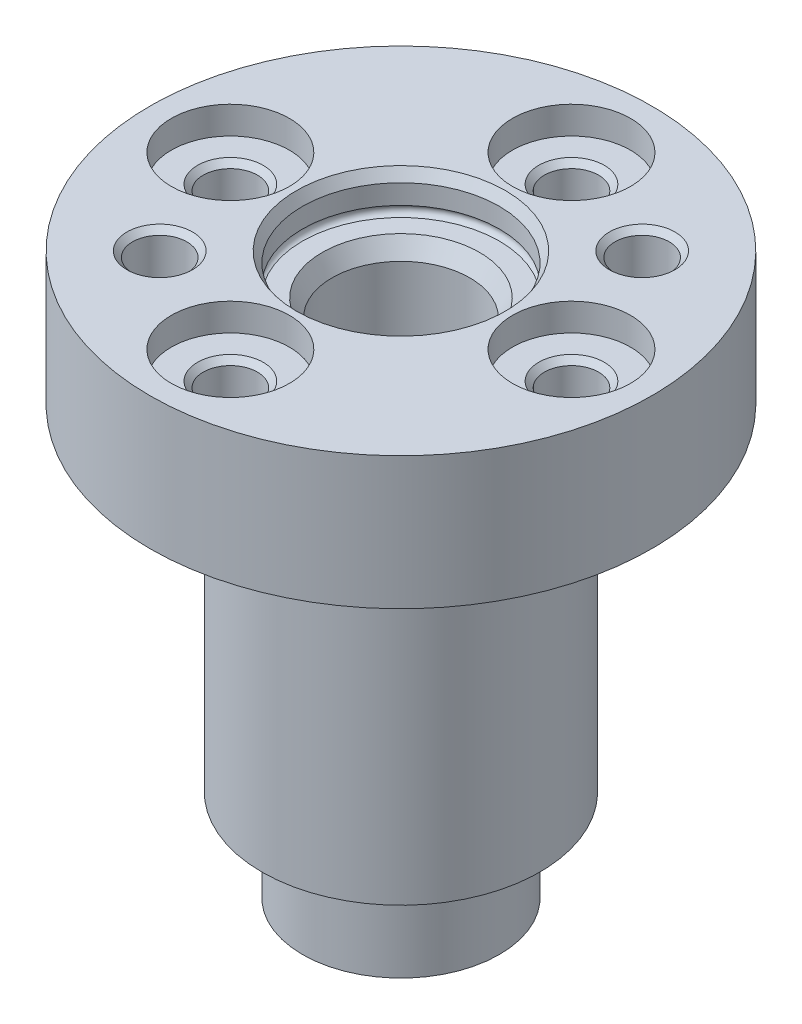
SolidWorks part; units mm, degrees
ref_plane "Front Plane" through (0, 0, 0) normal (0, 0, 1) x (1, 0, 0)
ref_plane "Top Plane" through (0, 0, 0) normal (0, 1, 0) x (1, 0, 0)
ref_plane "Right Plane" through (0, 0, 0) normal (1, 0, 0) x (0, 0, -1)
sketch "Sketch1" plane through (0, 0, 0) normal (0, 0, 1) x (1, 0, 0)
  line L0 (0, 42.7) -> (19.125, 42.7)
  line L1 (19.125, 42.7) -> (19.125, 32.6)
  line L2 (19.125, 32.6) -> (10.6, 32.6)
  line L3 (10.6, 32.6) -> (10.6, 7)
  line L4 (10.6, 7) -> (7.5, 7)
  line L5 (7.5, 7) -> (7.5, 0)
  line L6 (7.5, 0) -> (0, 0)
  line L7 (0, 0) -> (0, 42.7)
  line L8 (0, 0) -> (0, 42.7) construction
revolve "Revolve1" add sketch "Sketch1" angle 360 about L8 reverse direction yes
ref_plane "Plane1" through (0, 0, 0) normal (0, 0, -1) x (-1, 0, 0)
sketch "Sketch2" plane through (0, 0, 0) normal (0, 0, -1) x (-1, 0, 0)
  line L0 (0, 27.6) -> (17.125, 27.6)
  line L1 (17.125, 27.6) -> (17.125, 22.6)
  line L2 (17.125, 22.6) -> (0, 22.6)
  line L3 (0, 22.6) -> (0, 27.6)
  line L4 (0, 22.6) -> (0, 27.6) construction
revolve "Revolve2" add sketch "Sketch2" angle 4 about L4 other way angle 4 reverse direction yes
sketch "Sketch3" plane through (0, 0, 0) normal (0, 0, 1) x (1, 0, 0)
  line L0 (0, 42.7) -> (7.965, 42.7)
  line L1 (7.965, 42.7) -> (7.5, 41.8946)
  line L2 (7.5, 41.8946) -> (7.5, 40.4)
  line L3 (7.5, 39.6) -> (6.0006, 39.6)
  line L4 (6.0006, 39.6) -> (5.25, 38.3)
  line L5 (5.25, 38.3) -> (5.25, 1.5)
  line L6 (5.25, 1.5) -> (6.116, 0)
  line L7 (6.116, 0) -> (0, 0)
  line L8 (0, 0) -> (0, 42.7)
  line L9 (0, 0) -> (0, 42.7) construction
  arc A0 (7.5, 40.4) -> (7.5, 39.6) centre (7.3833, 40) cw
revolve "Cut-Revolve1" cut sketch "Sketch3" angle 360 about L9 reverse direction yes
sketch "Sketch4" plane through (0, 0, 0) normal (0, 0, 1) x (1, 0, 0)
  line L0 (13, 42.7) -> (17.5, 42.7)
  line L1 (17.5, 42.7) -> (17.5, 40.6)
  line L2 (17.5, 40.6) -> (15.5, 40.6)
  line L3 (15.5, 40.6) -> (15.067, 40.167)
  line L4 (15.067, 40.167) -> (15.067, 34.6)
  line L5 (15.067, 34.6) -> (13, 33.4066)
  line L6 (13, 33.4066) -> (13, 42.7)
  line L7 (13, 33.4066) -> (13, 42.7) construction
revolve "Cut-Revolve2" cut sketch "Sketch4" angle 360 about L7 reverse direction yes
cosmetic thread "Cosmetic Thread1" parameters "D1"=6, "D2"=5
sketch "Sketch5" plane through (0, 0, 0) normal (0, 0, 1) x (1, 0, 0)
  line L0 (-13, 42.7) -> (-8.5, 42.7)
  line L1 (-8.5, 42.7) -> (-8.5, 40.6)
  line L2 (-8.5, 40.6) -> (-10.5, 40.6)
  line L3 (-10.5, 40.6) -> (-10.933, 40.167)
  line L4 (-10.933, 40.167) -> (-10.933, 34.6)
  line L5 (-10.933, 34.6) -> (-13, 33.4066)
  line L6 (-13, 33.4066) -> (-13, 42.7)
  line L7 (-13, 33.4066) -> (-13, 42.7) construction
revolve "Cut-Revolve3" cut sketch "Sketch5" angle 360 about L7 reverse direction yes
cosmetic thread "Cosmetic Thread2" parameters "D1"=6, "D2"=5
sketch "Sketch6" plane through (0, 0, 0) normal (1, 0, 0) x (0, 0, -1)
  line L0 (13, 42.7) -> (17.5, 42.7)
  line L1 (17.5, 42.7) -> (17.5, 40.6)
  line L2 (17.5, 40.6) -> (15.5, 40.6)
  line L3 (15.5, 40.6) -> (15.067, 40.167)
  line L4 (15.067, 40.167) -> (15.067, 34.6)
  line L5 (15.067, 34.6) -> (13, 33.4066)
  line L6 (13, 33.4066) -> (13, 42.7)
  line L7 (13, 33.4066) -> (13, 42.7) construction
revolve "Cut-Revolve4" cut sketch "Sketch6" angle 360 about L7 reverse direction yes
cosmetic thread "Cosmetic Thread3" parameters "D1"=6, "D2"=5
sketch "Sketch7" plane through (0, 0, 0) normal (1, 0, 0) x (0, 0, -1)
  line L0 (-13, 42.7) -> (-8.5, 42.7)
  line L1 (-8.5, 42.7) -> (-8.5, 40.6)
  line L2 (-8.5, 40.6) -> (-10.5, 40.6)
  line L3 (-10.5, 40.6) -> (-10.933, 40.167)
  line L4 (-10.933, 40.167) -> (-10.933, 34.6)
  line L5 (-10.933, 34.6) -> (-13, 33.4066)
  line L6 (-13, 33.4066) -> (-13, 42.7)
  line L7 (-13, 33.4066) -> (-13, 42.7) construction
revolve "Cut-Revolve5" cut sketch "Sketch7" angle 360 about L7 reverse direction yes
cosmetic thread "Cosmetic Thread4" parameters "D1"=6, "D2"=5
ref_plane "Plane2" through (0, 0, 0) normal (0.7071, 0, 0.7071) x (0.7071, 0, -0.7071)
sketch "Sketch8" plane through (0, 0, 0) normal (0.7071, 0, 0.7071) x (0.7071, 0, -0.7071)
  line L0 (13, 42.7) -> (15.5, 42.7)
  line L1 (15.5, 42.7) -> (15.067, 42.267)
  line L2 (15.067, 42.267) -> (15.067, 34.6)
  line L3 (15.067, 34.6) -> (13, 33.4066)
  line L4 (13, 33.4066) -> (13, 42.7)
  line L5 (13, 33.4066) -> (13, 42.7) construction
revolve "Cut-Revolve6" cut sketch "Sketch8" angle 360 about L5 reverse direction yes
cosmetic thread "Cosmetic Thread5" parameters "D1"=6.6, "D2"=5
sketch "Sketch9" plane through (0, 0, 0) normal (0.7071, 0, 0.7071) x (0.7071, 0, -0.7071)
  line L0 (-13, 42.7) -> (-10.5, 42.7)
  line L1 (-10.5, 42.7) -> (-10.933, 42.267)
  line L2 (-10.933, 42.267) -> (-10.933, 34.6)
  line L3 (-10.933, 34.6) -> (-13, 33.4066)
  line L4 (-13, 33.4066) -> (-13, 42.7)
  line L5 (-13, 33.4066) -> (-13, 42.7) construction
revolve "Cut-Revolve7" cut sketch "Sketch9" angle 360 about L5 reverse direction yes
cosmetic thread "Cosmetic Thread6" parameters "D1"=6.6, "D2"=5
ref_plane "Plane3" through (0, 32.6, 0) normal (0, 1, 0) x (1, 0, 0)
ref_plane "Plane4" through (0, 42.7, 0) normal (0, 1, 0) x (1, 0, 0)
ref_plane "WELLEN XY" through (0, 32.6, 0) normal (0, 1, 0) x (1, 0, 0)
ref_plane "WELLEN XZ" through (0, 0, 0) normal (1, 0, 0) x (0, 0, -1)
ref_plane "WELLEN YZ" through (0, 0, 0) normal (0, 0, -1) x (-1, 0, 0)
ref_axis "WELLEN X" through (0, 32.6, 50) along (0, 0, -1)
ref_axis "WELLEN Y" through (80.9, 32.6, 0) along (-1, 0, 0)
ref_axis "WELLEN Z" through (0, 50, 0) along (0, -1, 0)
sketch3d "WELLEN"
  point P0 (0, 32.6, 0)
other "Freeze***"
